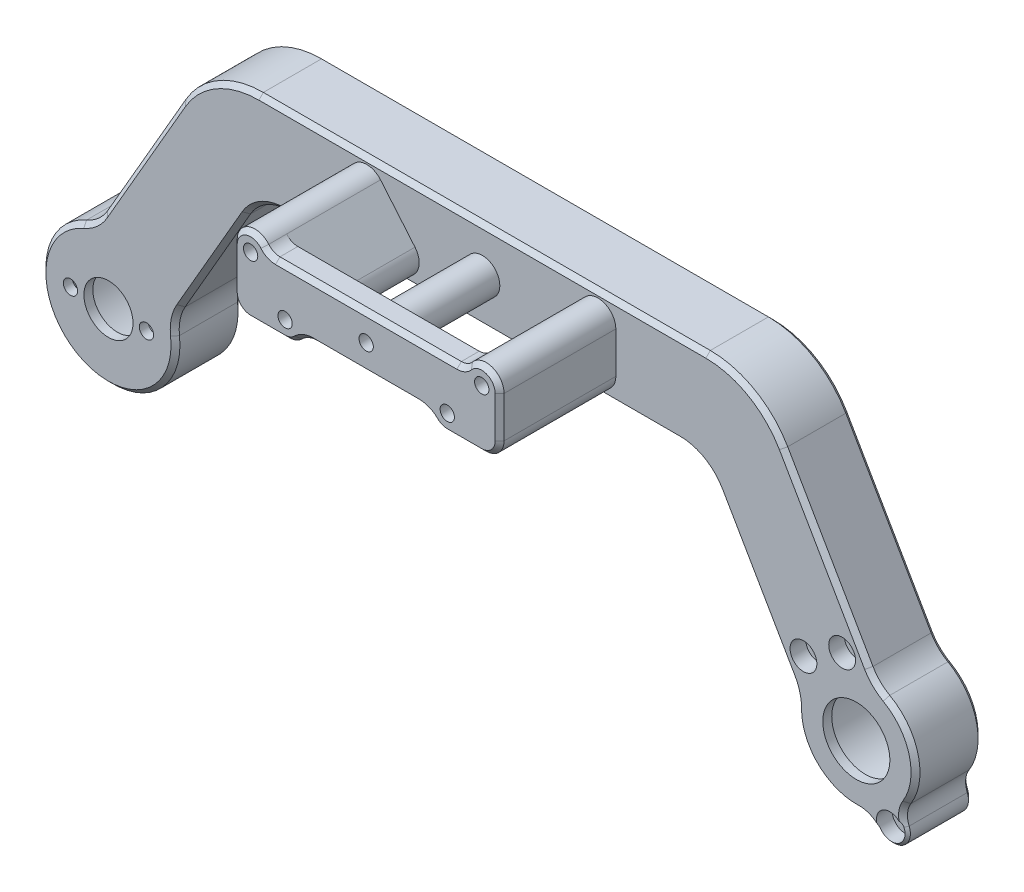
SolidWorks part; units mm, degrees
other "Markup1"
sketch "Sketch2"
ref_plane "Front Plane" through (0, 0, 0) normal (0, 0, 1) x (1, 0, 0)
ref_plane "Top Plane" through (0, 0, 0) normal (0, 1, 0) x (1, 0, 0)
ref_plane "Right Plane" through (0, 0, 0) normal (1, 0, 0) x (0, 0, -1)
ref_axis "X" through (-88.99, 0, 0) along (1, 0, 0)
ref_axis "Y" through (0, 55, 0) along (0, -1, 0)
ref_axis "Z" through (0, 0, -88.99) along (0, 0, 1)
sketch "Sketch1" plane through (0, 0, 0) normal (0, 0, 1) x (1, 0, 0)
  line L0 (0, 10) -> (0, -10) construction
  line L1 (-50, 10) -> (50, 10)
  line L2 (-50, -10) -> (50, -10)
  line L3 (67.3205, 0) -> (92.3205, -43.3013)
  line L4 (75, -53.3013) -> (50, -10)
  line L5 (-75, -53.3013) -> (-50, -10)
  line L6 (-67.3205, 0) -> (-92.3205, -43.3013)
  arc A0 (50, 10) -> (67.3205, 0) centre (50, -10) cw
  arc A1 (92.3205, -43.3013) -> (75, -53.3013) centre (83.6603, -48.3013) cw
  arc A3 (-92.3205, -43.3013) -> (-75, -53.3013) centre (-83.6603, -48.3013) ccw
  arc A4 (-50, 10) -> (-67.3205, 0) centre (-50, -10) ccw
  point P4 (0, 0)
  dimension "D1" = 20
  dimension "D2" = 50
  dimension "D3" = 60
  dimension "D4" = 50
extrude "Boss-Extrude1" add sketch "Sketch1" along normal mid plane 15
ref_plane "Plane1" through (0, 0, 28.5) normal (0, 0, 1) x (1, 0, 0)
sketch "Sketch3" plane through (0, 0, 0) normal (0, 0, 1) x (1, 0, 0)
  line L0 (-22, 0) -> (22, 0) construction
  line L1 (25.8567, 4.5963) -> (18.1433, -4.5963) construction
  line L2 (0, 0) -> (0, 1.6) construction
  line L3 (-25.8567, 4.5963) -> (-18.1433, -4.5963) construction
  circle A1 centre (0, 0) radius 1.6
  circle A2 centre (25.8567, 4.5963) radius 1.6
  circle A3 centre (18.1433, -4.5963) radius 1.6
  circle A4 centre (-25.8567, 4.5963) radius 1.6
  circle A5 centre (-18.1433, -4.5963) radius 1.6
  point P7 (0, 0)
  point P10 (22, 0)
  dimension "D6" = 3.2
  dimension "D3" = 12
  dimension "D4" = 22
  dimension "D5" = 50
extrude "Cut-Extrude1" cut sketch "Sketch3" against normal through all both and the other way through all
sketch "Sketch4" plane through (0, 0, 28.5) normal (0, 0, 1) x (1, 0, 0)
  line L0 (25.8567, 4.5963) -> (18.1433, -4.5963) construction
  line L1 (-25.8567, 4.5963) -> (-18.1433, -4.5963) construction
  line L2 (25.8567, 4.5963) -> (18.1433, -4.5963) construction
  line L3 (-25.8567, 4.5963) -> (-18.1433, -4.5963) construction
  line L4 (15.0791, -2.0251) -> (22.7925, 7.1674)
  line L5 (29.8567, 4.5963) -> (29.8567, -4.5963)
  line L6 (25.8567, -8.5963) -> (18.1433, -8.5963)
  line L7 (0, 0) -> (0, 1.6) construction
  line L8 (0, 0) -> (0, 1.6) construction
  line L9 (-25.8567, -8.5963) -> (-18.1433, -8.5963)
  line L10 (-29.8567, 4.5963) -> (-29.8567, -4.5963)
  line L11 (-15.0791, -2.0251) -> (-22.7925, 7.1674)
  line L12 (20.289, 6) -> (-20.289, 6)
  line L13 (0, 6) -> (0, 3.9)
  line L14 (0, -3.9) -> (0, -6)
  line L15 (-11.8193, -6) -> (11.8193, -6)
  circle A0 centre (25.8567, 4.5963) radius 1.6 construction
  circle A1 centre (18.1433, -4.5963) radius 1.6 construction
  circle A2 centre (-25.8567, 4.5963) radius 1.6 construction
  circle A3 centre (-18.1433, -4.5963) radius 1.6 construction
  circle A4 centre (0, 0) radius 1.6 construction
  circle A5 centre (25.8567, 4.5963) radius 1.6
  circle A6 centre (18.1433, -4.5963) radius 1.6
  circle A7 centre (-25.8567, 4.5963) radius 1.6
  circle A8 centre (-18.1433, -4.5963) radius 1.6
  circle A9 centre (0, 0) radius 1.6
  arc A10 (22.7925, 7.1674) -> (29.8567, 4.5963) centre (25.8567, 4.5963) cw
  arc A11 (29.8567, -4.5963) -> (25.8567, -8.5963) centre (25.8567, -4.5963) cw
  arc A12 (18.1433, -8.5963) -> (15.0791, -2.0251) centre (18.1433, -4.5963) cw
  arc A13 (-29.8567, -4.5963) -> (-25.8567, -8.5963) centre (-25.8567, -4.5963) ccw
  arc A14 (-22.7925, 7.1674) -> (-29.8567, 4.5963) centre (-25.8567, 4.5963) ccw
  arc A15 (-18.1433, -8.5963) -> (-15.0791, -2.0251) centre (-18.1433, -4.5963) ccw
  circle A16 centre (0, 0) radius 3.9
  arc A17 (22.7925, 7.1674) -> (20.289, 6) centre (20.289, 9.2681) cw
  arc A18 (11.8193, -6) -> (15.3326, -7.4424) centre (11.8193, -11) cw
  arc A19 (-11.8193, -6) -> (-15.3326, -7.4424) centre (-11.8193, -11) ccw
  arc A20 (-22.7925, 7.1674) -> (-20.289, 6) centre (-20.289, 9.2681) ccw
  dimension "D1" = 4
  dimension "D4" = 4
  dimension "D5" = 7.8
  dimension "D6" = 12
  dimension "D7" = 5
  dimension "D2" = 4
  dimension "D3" = 4
extrude "Boss-Extrude2" add sketch "Sketch4" against normal up to surface (21 mm away) separate body contours L9 A15 L11 A14 L10 A13 A8 A7 | A12 L6 A11 L5 A10 L4 A6 A5 | A16 A9 region at (23.3022, -1.3358, 28.5) region at (2.6797, 2.6797, 28.5) region at (-23.3022, -1.3358, 28.5) up to face at (-19.7433, -4.5963, 7.5)
extrude "Boss-Extrude3" add sketch "Sketch4<3>" along normal blind 5 contours L9 A15 L11 A14 L10 A13 A8 A7 | A20 L11 A15 A19 L15 L14 A16 L13 L12 | A16 A9 | L15 A18 A12 L4 A17 L12 L13 A16 L14 | A12 L6 A11 L5 A10 L4 A6 A5 region at (9.702, 0.5432, 28.5) region at (23.3022, -1.3358, 28.5) region at (-9.702, 0.5432, 28.5) region at (2.6797, 2.6797, 28.5) region at (-23.3022, -1.3358, 28.5)
sketch "Sketch4<3>" plane through (0, 0, 28.5) normal (0, 0, 1) x (1, 0, 0) same geometry as "Sketch4"
chamfer "Chamfer1" distance 1 angle 45 16 edges at (22, -8.5963, 33.5) (28.6852, -7.4247, 33.5) (16.6241, -8.2966, 33.5) (29.8567, 0, 33.5) (13.7183, -6.3746, 33.5) (27.2248, 8.355, 33.5) (0, -6, 33.5) (21.6702, 6.3062, 33.5) (-13.7183, -6.3746, 33.5) (0, 6, 33.5) (-16.6241, -8.2966, 33.5) (-21.6702, 6.3062, 33.5) (-22, -8.5963, 33.5) (-27.2248, 8.355, 33.5) (-28.6852, -7.4247, 33.5) (-29.8567, 0, 33.5)
sketch "Sketch5" plane through (0, 0, 0) normal (0, 0, 1) x (1, 0, 0)
  line L0 (-92.1603, -48.3013) -> (-75.1603, -48.3013) construction
  circle A1 centre (83.6603, -48.3013) radius 13.25
  circle A3 centre (83.6603, -48.3013) radius 11.25
  circle A4 centre (83.6603, -48.3013) radius 7.5
  circle A5 centre (-83.6603, -48.3013) radius 13
  circle A6 centre (-83.6603, -48.3013) radius 15
  circle A7 centre (-83.6603, -48.3013) radius 5.5
  circle A8 centre (-75.1603, -48.3013) radius 1.6
  circle A9 centre (-92.1603, -48.3013) radius 1.6
  point P14 (-83.6603, -48.3013)
  dimension "D1" = 2
  dimension "D2" = 22.5
  dimension "D3" = 15
  dimension "D4" = 26
  dimension "D6" = 11
  dimension "D8" = 3.2
  dimension "D7" = 17
  dimension "D5" = 2
extrude "Boss-Extrude4" add sketch "Sketch5" along normal up to surface and the other way up to surface contours A1 A3 region at (70.785, -48.3013, 0) up to face at (-19.7433, -4.5963, 7.5) other way up to face at (-19.7433, -4.5963, -7.5)
extrude "Cut-Extrude2" cut sketch "Sketch5<3>" against normal through all both and the other way through all contours A3
sketch "Sketch5<3>" plane through (0, 0, 0) normal (0, 0, 1) x (1, 0, 0) same geometry as "Sketch5"
extrude "Boss-Extrude5" add sketch "Sketch5<4>" against normal blind 2 from surface contours A3 A4 region at (72.7285, -48.3013, 0) starting at face at (72.4103, -48.3013, 7.5)
sketch "Sketch5<4>" plane through (0, 0, 0) normal (0, 0, 1) x (1, 0, 0) same geometry as "Sketch5"
extrude "Cut-Extrude3" cut sketch "Sketch5<5>" against normal through all both and the other way through all contours A5
sketch "Sketch5<5>" plane through (0, 0, 0) normal (0, 0, 1) x (1, 0, 0) same geometry as "Sketch5"
extrude "Boss-Extrude6" add sketch "Sketch5<6>" along normal up to surface (7.5 mm away) and the other way up to surface (7.5 mm away) contours A6 A5 region at (-98.236, -48.3013, 0) up to face at (1.2932, -17.4059, 7.5) other way up to face at (1.2932, -17.4059, -7.5)
sketch "Sketch5<6>" plane through (0, 0, 0) normal (0, 0, 1) x (1, 0, 0) same geometry as "Sketch5"
extrude "Boss-Extrude7" add sketch "Sketch5<7>" against normal blind 2 from surface contours A5 A9 A7 A8 region at (-96.2926, -48.3013, 0) starting at face at (0.0369, -19.5819, 7.5)
sketch "Sketch5<7>" plane through (0, 0, 0) normal (0, 0, 1) x (1, 0, 0) same geometry as "Sketch5"
fillet "Fillet1" radius 10 6 edges at (87.9742, -35.7732, 0) (70.6537, -45.7732, 0) (-86.7303, -33.6188, 0) (-69.4098, -43.6188, 0) (50, -10, 0) (-50, -10, 0)
sketch "Sketch6" plane through (0, 0, 0) normal (0, 0, 1) x (1, 0, 0)
  line L0 (71.8301, -37.8109) -> (80.4904, -32.8109) construction
  line L1 (76.1603, -35.3109) -> (83.6603, -48.3013) construction
  line L2 (83.6603, -48.3013) -> (91.1603, -61.2917) construction
  line L3 (75, -53.3013) -> (50, -10) construction
  circle A0 centre (91.1603, -61.2917) radius 1.6
  circle A1 centre (80.4904, -32.8109) radius 1.6
  circle A2 centre (71.8301, -37.8109) radius 1.6
  arc A3 (88.3078, -63.488) -> (94.4885, -59.9195) centre (91.1603, -61.2917) ccw
  arc A4 (94.4885, -59.9195) -> (94.878, -55.3529) centre (99.1111, -58.0138) cw
  circle A5 centre (83.6603, -48.3013) radius 13.25 construction
  arc A6 (88.3078, -63.488) -> (84.1582, -61.5419) centre (84.3462, -66.5384) ccw
  arc A7 (84.1582, -61.5419) -> (94.878, -55.3529) centre (83.6603, -48.3013) ccw
  dimension "D4" = 3.2
  dimension "D5" = 2
  dimension "D6" = 5
  dimension "D1" = 10
  dimension "D2" = 15
  dimension "D3" = 15
extrude "Boss-Extrude8" add sketch "Sketch6" along normal up to surface (7.5 mm away) and the other way up to surface (7.5 mm away) contours A7 A6 A3 A4 A0 region at (86.5301, -61.8816, 0) up to face at (0.2077, -23.3873, 7.5) other way up to face at (0.2077, -23.3873, -7.5)
extrude "Cut-Extrude4" cut sketch "Sketch6<3>" against normal through all both and the other way through all contours A2 | A1 | A0 region at (91.1603, -61.2917, 0) region at (80.4904, -32.8109, 0) region at (71.8301, -37.8109, 0)
sketch "Sketch6<3>" plane through (0, 0, 0) normal (0, 0, 1) x (1, 0, 0) same geometry as "Sketch6"
sketch "Sketch7" plane through (0, 0, 0) normal (0, 0, 1) x (1, 0, 0)
  circle A0 centre (80.4904, -32.8109) radius 3
  circle A1 centre (71.8301, -37.8109) radius 3
  circle A2 centre (91.1603, -61.2917) radius 3
  dimension "D1" = 6
extrude "Cut-Extrude5" cut sketch "Sketch7" against normal blind 3.5 from surface starting at face at (70.2301, -37.8109, 7.5)
chamfer "Chamfer2" distance 1 angle 45 38 edges at (0, -10, -7.5) (49.2265, -11.3397, -7.5) (-49.2265, -11.3397, -7.5) (60.9794, -29.0169, -7.5) (-60.1934, -27.6554, -7.5) (70.0858, -45.5012, -7.5) (-68.6367, -43.3061, -7.5) (-91.1603, -61.2917, -7.5) (88.0225, -35.1454, -7.5) (-86.8461, -32.7929, -7.5) (76.8565, -16.5169, -7.5) (-76.0705, -15.1554, -7.5) (60, 7.3205, -7.5) (-60, 7.3205, -7.5) (0, 10, -7.5) (0, -10, 7.5) (49.2265, -11.3397, 7.5) (-49.2265, -11.3397, 7.5) (60.9794, -29.0169, 7.5) (-60.1934, -27.6554, 7.5) (70.0858, -45.5012, 7.5) (-68.6367, -43.3061, 7.5) (-91.1603, -61.2917, 7.5) (88.0225, -35.1454, 7.5) (-86.8461, -32.7929, 7.5) (76.8565, -16.5169, 7.5) (-76.0705, -15.1554, 7.5) (60, 7.3205, 7.5) (-60, 7.3205, 7.5) (0, 10, 7.5) (86.4692, -62.0115, -7.5) (92.9603, -64.4093, -7.5) (94.1292, -57.5889, -7.5) (96.5024, -45.0391, -7.5) (74.4141, -57.7918, 7.5) (86.4692, -62.0115, 7.5) (92.9603, -64.4093, 7.5) (94.1292, -57.5889, 7.5)
mirror "Mirror1" [suppressed] about plane through (0, 0, 0) normal (0, 0, 1) of bodies 115 106
delete or keep bodies "Body-Delete/Keep 1" [suppressed] type keep bodies bodies 117 116
